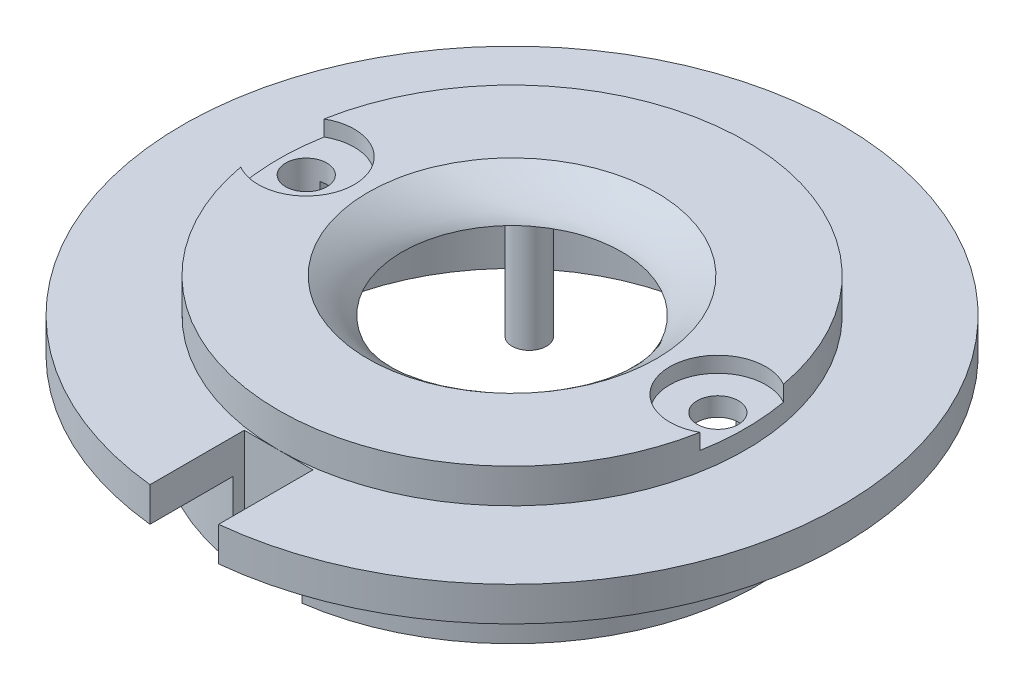
SolidWorks part; units mm, degrees
material "ABS"
ref_plane "Front Plane" through (0, 0, 0) normal (0, 0, 1) x (1, 0, 0)
ref_plane "Top Plane" through (0, 0, 0) normal (0, 1, 0) x (1, 0, 0)
ref_plane "Right Plane" through (0, 0, 0) normal (1, 0, 0) x (0, 0, -1)
sketch "Sketch1" plane through (0, 0, 0) normal (0, 1, 0) x (1, 0, 0)
  circle A0 centre (0, 0) radius 11.43
  circle A1 centre (0, 0) radius 10.16
  circle A2 centre (0, 0) radius 3.8 construction
  dimension "D1" = 1.27
  dimension "D2" = 22.86
ref_plane "Plane1" through (0, 3.175, 0) normal (0, 1, 0) x (1, 0, 0)
sketch "Sketch2" plane through (0, 3.175, 0) normal (0, 1, 0) x (1, 0, 0)
  circle A0 centre (0, 0) radius 16.51
  circle A1 centre (0, 0) radius 13.335
  dimension "D1" = 3.175
  dimension "D2" = 33.02
loft "Loft1" add section "Sketch1" section "Sketch2" connector at (10.0812, 0, 5.3865) connector at (16.2985, 3.175, 2.6339)
sketch "Sketch3" plane through (0, 3.175, 0) normal (0, 1, 0) x (1, 0, 0)
  circle A1 centre (0, 0) radius 13.335
  circle A2 centre (0, 0) radius 13.335
  circle A3 centre (0, 0) radius 16.51
  circle A4 centre (0, 0) radius 16.51
  dimension "D1" = 0
  dimension "D2" = 0
sketch "Sketch4" plane through (0, 0, 0) normal (0, -1, 0) x (1, 0, 0)
  circle A1 centre (0, 0) radius 10.16
  circle A2 centre (0, 0) radius 10.16
  circle A3 centre (0, 0) radius 11.43
  circle A4 centre (0, 0) radius 11.43
  dimension "D1" = 0
  dimension "D2" = 0
loft "Cut-Loft1" cut section "Sketch3" section "Sketch4" connector at (11.7177, 3.175, 6.3654) connector at (5.2595, 0, 8.6927)
sketch "Sketch5" plane through (0, 3.175, 0) normal (0, 1, 0) x (1, 0, 0)
  circle A0 centre (0, 0) radius 22.8434
  circle A3 centre (0, 0) radius 13.335
  circle A4 centre (0, 0) radius 3.8 construction
  circle A5 centre (0, 0) radius 13.335 construction
  arc A6 (14.2879, -17.8235) -> (-13.6477, -18.3184) centre (0, 0) ccw construction
extrude "Boss-Extrude2" add sketch "Sketch5" against normal blind 3.175
sketch "Sketch10" plane through (0, 0, 0) normal (0, 0, 1) x (1, 0, 0)
  line L0 (-13.335, 1.3057) -> (-10.16, 0)
  line L1 (-10.16, 0) -> (-13.335, 0)
  line L2 (-13.335, 0) -> (-13.335, 1.3057)
  line L3 (-13.335, 1.3057) -> (13.335, 1.3057) construction
  line L4 (-13.335, 0) -> (13.335, 0) construction
  line L5 (-11.43, 0) -> (11.43, 0) construction
  line L6 (-10.16, 0) -> (10.16, 0) construction
  line L7 (-13.335, 1.3057) -> (-13.335, 0) construction
revolve "Revolve4" add sketch "Sketch10" angle 360 about axis through (0, -10.16, 0) along (0, 1, 0)
sketch "Sketch8" plane through (0, 0, 0) normal (0, -1, 0) x (-1, 0, 0)
  circle A0 centre (0, 0) radius 22.8434
  circle A2 centre (0, 0) radius 19.6684
  circle A5 centre (0, 0) radius 22.8434 construction
  dimension "D1" = 3.175
extrude "Boss-Extrude3" add sketch "Sketch8" along normal blind 10.16 contours A0 | A2
sketch "Sketch9" plane through (0, 3.175, 0) normal (0, 1, 0) x (1, 0, 0)
  line L0 (13.335, 0) -> (19.0334, 0) construction
  line L1 (19.0334, 0) -> (22.8434, 0) construction
  line L2 (-19.0334, 0) -> (-13.335, 0) construction
  line L3 (-19.0334, 0) -> (-22.8434, 0) construction
  circle A0 centre (19.0334, 0) radius 1.905
  circle A1 centre (-19.0334, 0) radius 1.905
  circle A6 centre (0, 0) radius 13.335 construction
  circle A7 centre (0, 0) radius 22.8434 construction
  dimension "D1" = 3.81
  dimension "D2" = 3.81
  dimension "D3" = 3.81
extrude "Cut-Extrude2" cut sketch "Sketch9" against normal through all both and the other way through all
ref_axis "Axis1" through (0, -10.16, 0) along (0, 1, 0)
sketch "Sketch11" plane through (0, 3.175, 0) normal (0, 1, 0) x (1, 0, 0)
  circle A0 centre (0, 0) radius 21.59
  circle A1 centre (0, 0) radius 22.8434
  circle A2 centre (0, 0) radius 22.8434 construction
  dimension "D1" = 43.18
extrude "Cut-Extrude3" cut sketch "Sketch11" against normal blind 3.175
sketch "Sketch12" plane through (0, 0, 0) normal (0, 1, 0) x (1, 0, 0)
  circle A0 centre (0, 0) radius 30.48
  circle A2 centre (0, 0) radius 21.59 construction
  circle A3 centre (0, 0) radius 21.59
  dimension "D1" = 8.89
extrude "Boss-Extrude4" add sketch "Sketch12" against normal blind 3.175 contours A0 | A3
sketch "Sketch13" plane through (0, 0, 0) normal (0, 1, 0) x (1, 0, 0)
  line L1 (-3.175, -21.59) -> (3.175, -21.59)
  line L2 (-3.175, -21.59) -> (-3.175, -30.48)
  line L3 (-3.175, -30.48) -> (3.175, -30.48)
  line L4 (3.175, -21.59) -> (3.175, -30.48)
  line L5 (-3.175, -21.59) -> (3.175, -30.48) construction
  line L6 (-3.175, -30.48) -> (3.175, -21.59) construction
  circle A0 centre (0, 0) radius 21.59 construction
  circle A1 centre (0, 0) radius 30.48 construction
  point P0 (0, -26.035)
  point P5 (0, -21.59)
  point P8 (0, -30.48)
  dimension "D1" = 6.35
extrude "Cut-Extrude4" cut sketch "Sketch13" against normal through all both and the other way through all
sketch "Sketch14" plane through (0, 3.175, 0) normal (0, 1, 0) x (1, 0, 0)
  circle A0 centre (-19.0334, 0) radius 4.445
  circle A1 centre (19.0334, 0) radius 4.445
  dimension "D1" = 8.89
extrude "Cut-Extrude5" cut sketch "Sketch14" against normal blind 1.4478
sketch "Sketch15" plane through (0, 0, 0) normal (0, -1, 0) x (1, 0, 0)
  line L0 (10.2769, -12.684) -> (0, 0) construction
  line L1 (0, 0) -> (-10.7198, -12.3121) construction
  circle A0 centre (10.2769, -12.684) radius 1.5875
  circle A1 centre (-10.7198, -12.3121) radius 1.5875
  circle A4 centre (-10.7198, -12.3121) radius 1.27 construction
  circle A5 centre (10.2769, -12.684) radius 1.27 construction
  dimension "D1" = 3.175
extrude "Boss-Extrude5" add sketch "Sketch15" along normal up to surface (13.21 mm away)
sketch "Sketch16" plane through (0, -13.21, 0) normal (0, -1, 0) x (-1, 0, 0)
  circle A0 centre (10.7198, 12.3121) radius 1.27
  circle A1 centre (-10.2769, 12.684) radius 1.27
  circle A2 centre (-10.2769, 12.684) radius 1.27 construction
extrude "Cut-Extrude6" cut sketch "Sketch16" against normal blind 3.175
